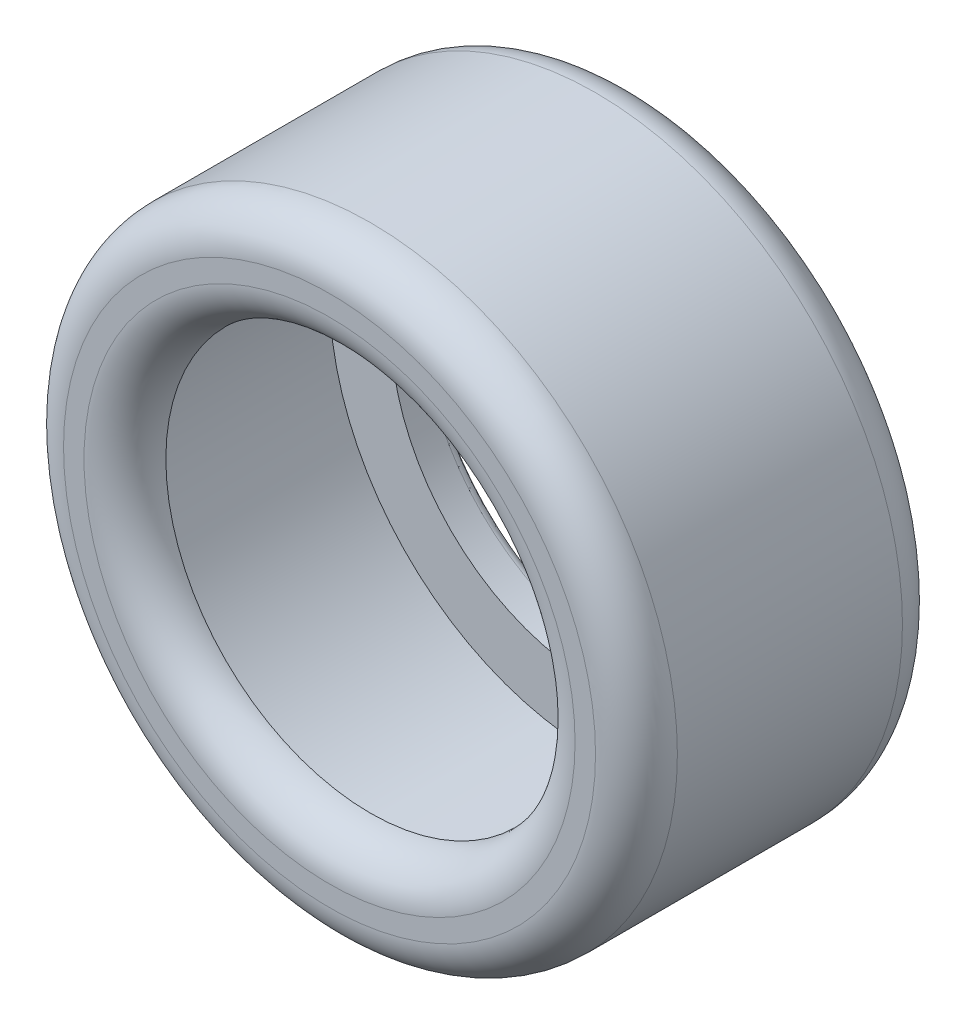
SolidWorks part; units mm, degrees
ref_plane "Front Plane" through (0, 0, 0) normal (0, 0, 1) x (1, 0, 0)
ref_plane "Top Plane" through (0, 0, 0) normal (0, 1, 0) x (1, 0, 0)
ref_plane "Right Plane" through (0, 0, 0) normal (1, 0, 0) x (0, 0, -1)
sketch "Sketch1" plane through (0, 0, 0) normal (0, 0, 1) x (1, 0, 0)
  circle A0 centre (0, 0) radius 10
  dimension "D1" = 20
extrude "Extrude-Thin1" add sketch "Sketch1" along normal blind 15 thin thin type one direction wall 5
fillet "Fillet1" radius 2 3 edges at (10, 0, 15) (15, 0, 15) (15, 0, 0)
fillet "Fillet2" radius 0.5 1 edges at (10, 0, 0)
shell "Shell5" thickness 2 removed face at (10, 0, 0.5)
sketch "Sketch3" plane through (0, 0, 0) normal (0, 0, 1) x (1, 0, 0)
  line L0 (0, 14.989) -> (0, 0) construction
